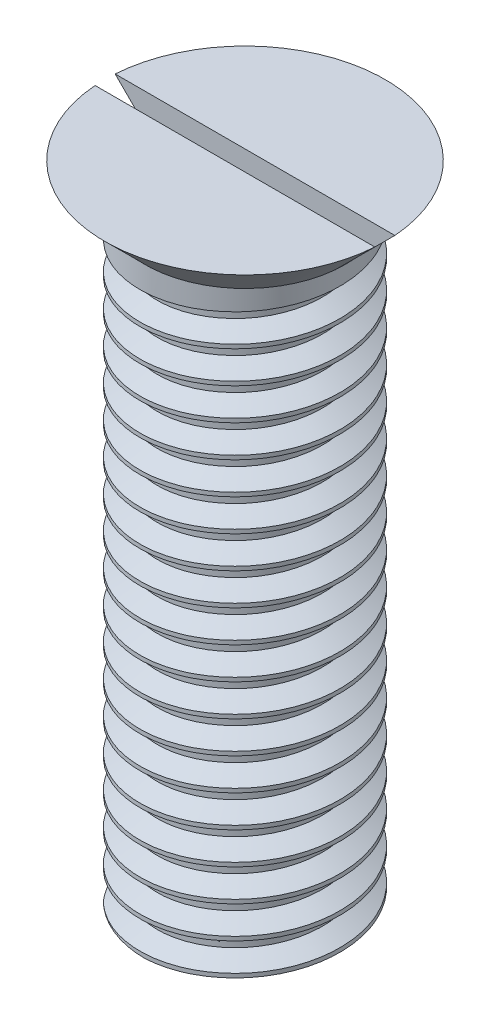
SolidWorks part; units mm, degrees
ref_plane "Front Plane" through (0, 0, 0) normal (0, 0, 1) x (1, 0, 0)
ref_plane "Top Plane" through (0, 0, 0) normal (0, 1, 0) x (1, 0, 0)
ref_plane "Right Plane" through (0, 0, 0) normal (1, 0, 0) x (0, 0, -1)
sketch "Sketch1" plane through (0, 0, 0) normal (0, 1, 0) x (1, 0, 0)
  circle A0 centre (0, 0) radius 2.5
extrude "Boss-Extrude1" add sketch "Sketch1" along normal blind 15
thread "Thread1" pitch 0.8 method cut profile "Thread Profile1" start angle 0, offset 0, length 15, pitch 0.8, diameter 5
ref_plane "Plane1" through (-2.5, 15, 0) normal (0, 0, 1) x (-1, 0, 0)
sketch "Thread Profile1" plane through (-2.5, 15, 0) normal (0, 0, 1) x (-1, 0, 0)
  line L0 (0, 0) -> (0, 0.8) construction
  line L11 (0, 0) -> (0, 0.7)
  line L12 (0, 0.7) -> (-0.433, 0.45)
  line L13 (-0.433, 0.45) -> (-0.433, 0.25)
  line L15 (-0.433, 0.25) -> (0, 0)
  line L17 (-0.433, 0.35) -> (0, 0.35) construction
  point P2 (0, 0)
  dimension "Pitch" = 0.8
  dimension "Profile_Angle" = 60
  dimension "Profile_Land" = 0.2
  dimension "Profile_Height" = 0.433
sketch "Sketch4" plane through (0, 15, 0) normal (0, 1, 0) x (1, 0, 0)
  line L0 (2.4875, 0.25) -> (2.5, 0.25)
  line L1 (-2.5, 0.25) -> (-2.5, -0.25)
  line L2 (2.5, 0.25) -> (2.5, -0.25)
  line L3 (-2.5, -0.25) -> (-2.4875, -0.25)
  line L4 (-2.5, 0.25) -> (-2.4875, 0.25)
  line L5 (2.4875, -0.25) -> (2.5, -0.25)
  circle A1 centre (0, 0) radius 2.5
  circle M6 centre (0, 0) radius 2.5
extrude "Boss-Extrude4" add sketch "Sketch4" along normal blind 1 draft 45 contours A1 M6 region at (0, 15, 0) draft outward yes
sketch "Sketch5" plane through (0, 16, 0) normal (0, 1, 0) x (1, 0, 0)
  line L0 (3.5, 0) -> (-3.5, 0)
  line L1 (3.5, 0.25) -> (-3.5, 0.25)
  line L2 (3.5, -0.25) -> (-3.5, -0.25)
  line L3 (-3.5, 0.25) -> (-3.5, -0.25)
  line L4 (3.5, 0.25) -> (3.5, -0.25)
  circle A0 centre (0, 0) radius 3.5 construction
  circle M2 centre (0, 0) radius 3.5
extrude "Cut-Extrude1" cut sketch "Sketch5" against normal blind 1 contours L1 L0 M2 | L2 L0 M2 region at (0, 16, 0.1249) region at (0, 16, -0.1249)
